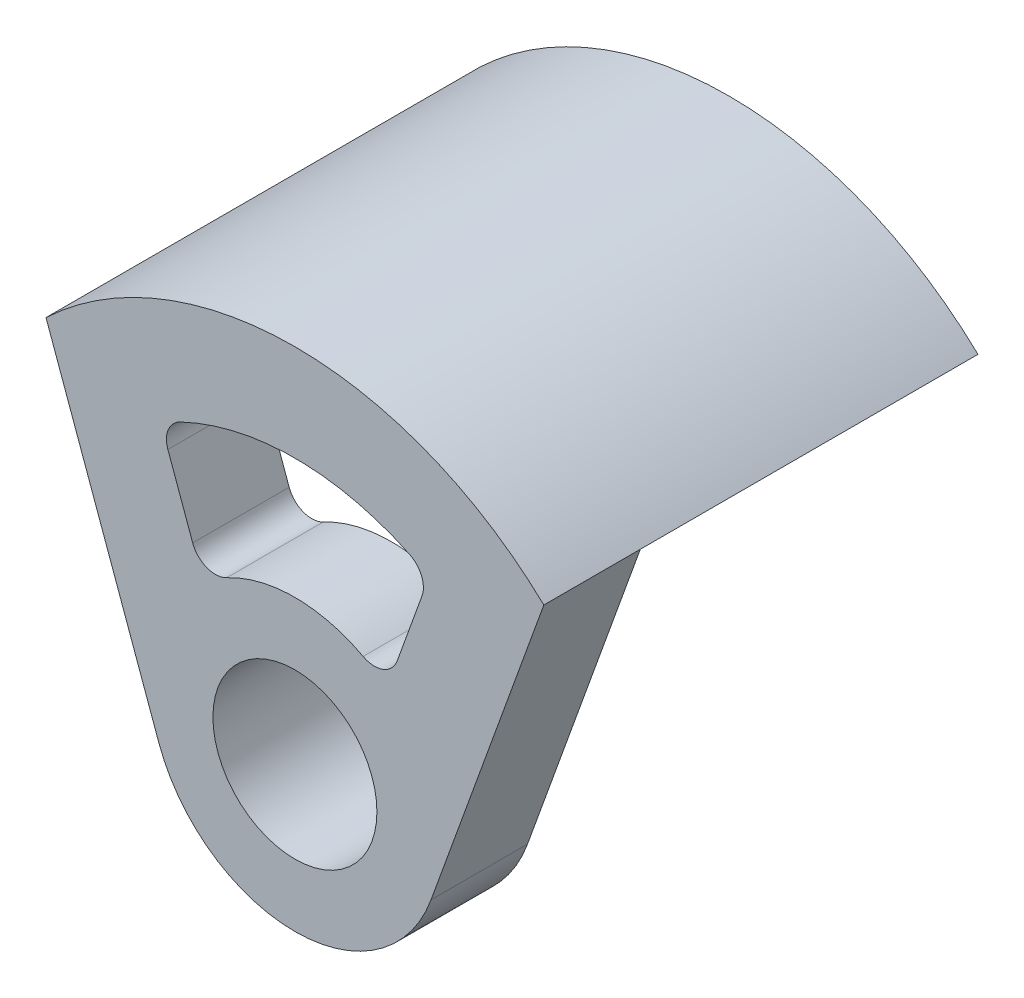
SolidWorks part; units mm, degrees
ref_plane "Front Plane" through (0, 0, 0) normal (0, 0, 1) x (1, 0, 0)
ref_plane "Top Plane" through (0, 0, 0) normal (0, 1, 0) x (1, 0, 0)
ref_plane "Right Plane" through (0, 0, 0) normal (1, 0, 0) x (0, 0, -1)
sketch "Sketch1" plane through (0, 0, 0) normal (0, 0, 1) x (1, 0, 0)
  line L0 (4.5962, 4.5962) -> (5.3033, 5.3033) construction
  line L1 (-4.5962, 4.5962) -> (-5.3033, 5.3033) construction
  line L2 (4.5962, 4.5962) -> (5.3033, 5.3033)
  line L3 (-4.5962, 4.5962) -> (-5.3033, 5.3033)
  line L4 (4.5941, 4.8769) -> (5.1619, 5.4447)
  line L5 (-4.5941, 4.8769) -> (-5.1619, 5.4447)
  arc A0 (4.5962, 4.5962) -> (-4.5962, 4.5962) centre (0, 0) ccw construction
  arc A1 (4.5962, 4.5962) -> (-4.5962, 4.5962) centre (0, 0) ccw
  circle A2 centre (0, 0) radius 7.5
  arc A4 (4.5941, 4.8769) -> (-4.5941, 4.8769) centre (0, 0) ccw
  dimension "D1" = 0.2
extrude "Boss-Extrude1" add sketch "Sketch1" against normal up to surface (2 mm away) contours A4 L4 A2 L5 region at (4.8017, 5.2352, 0)
extrude "Boss-Extrude2" add sketch "Sketch1<3>" along normal blind 5 contours A4 L4 A2 L5 region at (4.8017, 5.2352, 0)
sketch "Sketch1<3>" plane through (0, 0, 0) normal (0, 0, 1) x (1, 0, 0) same geometry as "Sketch1"
sketch "Sketch3" plane through (0, 0, 5) normal (0, 0, 1) x (1, 0, 0)
  line L0 (-5.16, 5.4428) -> (-2.821, -1.0208)
  line L1 (5.16, 5.4428) -> (2.821, -1.0208)
  line L2 (2.7807, 4.7453) -> (1.9028, 2.3194)
  line L3 (-2.7807, 4.7453) -> (-1.9028, 2.3194)
  line L4 (-2.7807, 4.7453) -> (-0.9403, -0.3403) construction
  line L5 (2.7807, 4.7453) -> (0.9403, -0.3403) construction
  circle A0 centre (0, 0) radius 3
  circle A1 centre (0, 0) radius 1.7 construction
  arc A2 (5.16, 5.4428) -> (-5.16, 5.4428) centre (0, 0) ccw construction
  arc A3 (5.16, 5.4428) -> (-5.16, 5.4428) centre (0, 0) ccw
  arc A4 (2.7807, 4.7453) -> (-2.7807, 4.7453) centre (0, 0) ccw
  circle A6 centre (0, 0) radius 1.7
  arc M3 (-4.5941, 4.8769) -> (4.5941, 4.8769) centre (0, 0) cw
  line M4 (4.5941, 4.8769) -> (5.16, 5.4428)
  arc M5 (5.16, 5.4428) -> (-5.16, 5.4428) centre (0, 0) ccw
  line M6 (-5.16, 5.4428) -> (-4.5941, 4.8769)
  dimension "D1" = 6
  dimension "D2" = 2
extrude "Boss-Extrude3" add sketch "Sketch3" along normal blind 2 contours A4 L2 A0 L1 L0 L3 M4 M3 M6 | M6 M3 M4 M5 | A0 A6 region at (-4.9682, 5.0687, 5) region at (0, 7.3935, 5) region at (-2.8109, 0.7727, 5)
sketch "Sketch4" plane through (0, 0, 5) normal (0, 0, -1) x (-1, 0, 0)
  circle A2 centre (0, 0) radius 2.2
  circle A3 centre (0, 0) radius 2.2
  circle M6 centre (0, 0) radius 1.7
  dimension "D1" = 0.5
extrude "Boss-Extrude4" add sketch "Sketch4" along normal blind 0.5 contours A3 M6 region at (2.1378, 0, 5)
chamfer "Chamfer1" distance 0.5 angle 45 1 edges at (2.2, 0, 5)
fillet "Fillet1" radius 0.5 4 edges at (1.9028, 2.3194, 6) (-1.9028, 2.3194, 6) (2.7807, 4.7453, 6) (-2.7807, 4.7453, 6)
